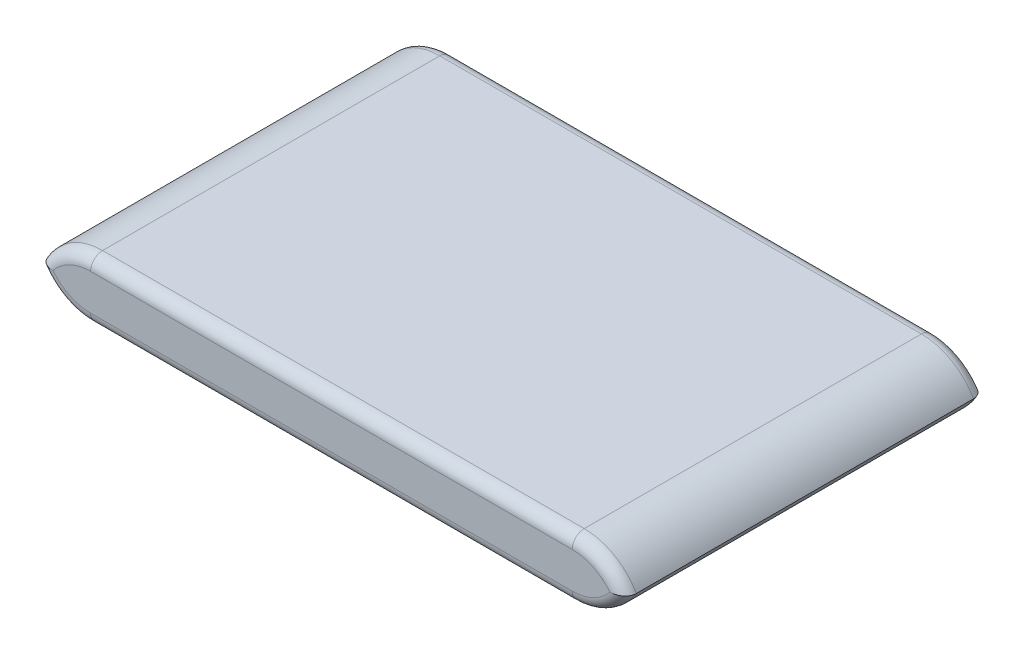
SolidWorks part; units mm, degrees
ref_plane "Front Plane" through (0, 0, 0) normal (0, 0, 1) x (1, 0, 0)
ref_plane "Top Plane" through (0, 0, 0) normal (0, 1, 0) x (1, 0, 0)
ref_plane "Right Plane" through (0, 0, 0) normal (1, 0, 0) x (0, 0, -1)
sketch "Sketch1" plane through (0, 0, 0) normal (0, 1, 0) x (1, 0, 0)
  line L1 (-25, 15) -> (25, 15)
  line L2 (-25, 15) -> (-25, -15)
  line L3 (-25, -15) -> (25, -15)
  line L4 (25, 15) -> (25, -15)
  line L5 (-25, 15) -> (25, -15) construction
  line L6 (-25, -15) -> (25, 15) construction
  point P0 (0, 0)
  dimension "D1" = 30
  dimension "D2" = 50
extrude "Boss-Extrude1" add sketch "Sketch1" along normal blind 5
fillet "Fillet1" radius 5 4 edges at (-25, 0, 0) (-25, 5, 0) (25, 0, 0) (25, 5, 0)
fillet "Fillet2" radius 1 12 edges at (22.5, 0.6699, -15) (22.5, 4.3301, -15) (0, 5, -15) (-22.5, 4.3301, -15) (-22.5, 0.6699, -15) (0, 0, -15) (0, 5, 15) (22.5, 4.3301, 15) (22.5, 0.6699, 15) (0, 0, 15) (-22.5, 0.6699, 15) (-22.5, 4.3301, 15)
